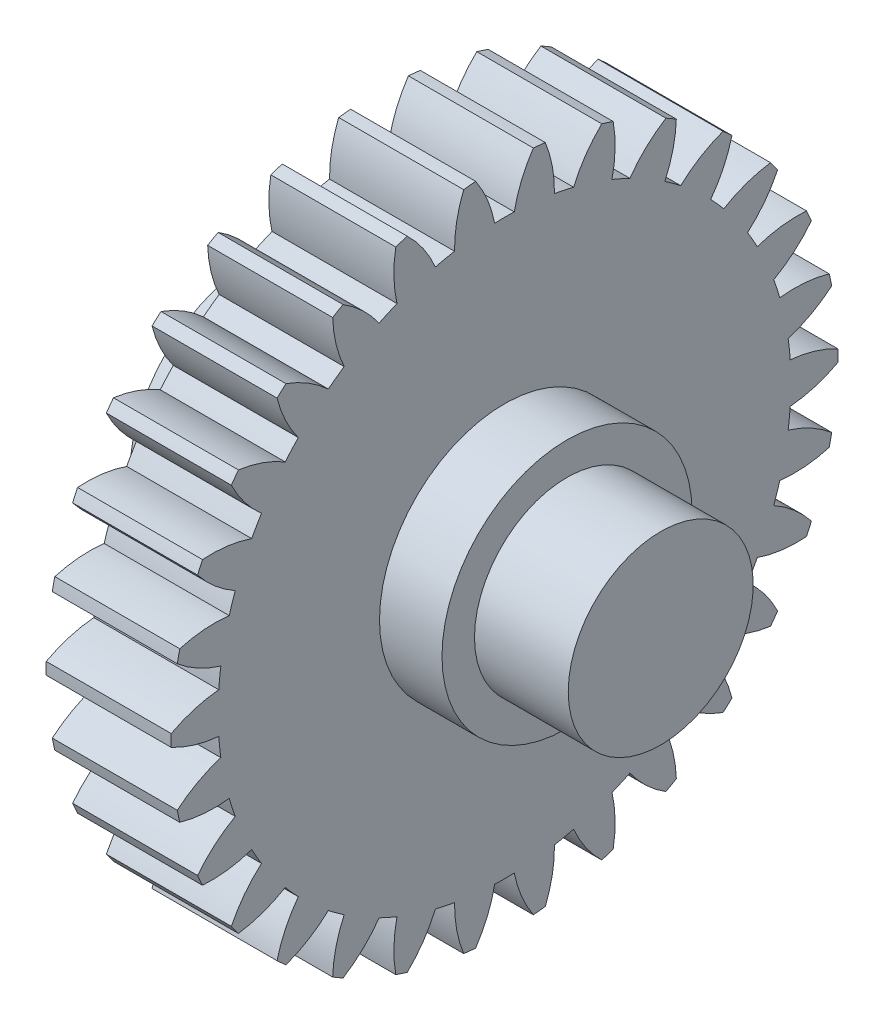
SolidWorks part; units mm, degrees
ref_plane "Plane1" through (0, 0, 0) normal (0, 0, 1) x (1, 0, 0)
ref_plane "Plane2" through (0, 0, 0) normal (0, 1, 0) x (1, 0, 0)
ref_plane "Plane3" through (0, 0, 0) normal (1, 0, 0) x (0, 0, -1)
other "Configuration Table"
sketch "HoldingSke" plane through (0, 0, 0) normal (0, 1, 0) x (1, 0, 0)
  line L0 (0, 0) -> (263.9645, -152.4)
  line L1 (-15, 0) -> (100, 0) construction
  line L2 (0, 0) -> (-2.1039, 2.3779)
  line L3 (0, 0) -> (-11.863, 4.5341)
  line L4 (0, 0) -> (7.479, 4.318)
  line L5 (0, 0) -> (-47.5972, -17.7524)
  line L6 (0, 0) -> (-10.5278, -7.1032)
  line L7 (-2.1039, 2.3779) -> (8.8311, 51.9886)
  line L8 (-76.2, 54.61) -> (-54.9402, 54.61)
  line L9 (-71.009, 38.7566) -> (-53.1078, 45.2721)
  line L10 (-76.2, 71.12) -> (104.1128, 71.12)
  line L11 (0, 0) -> (-12.7, 0)
  line L12 (-76.2, 101.6) -> (-76.1147, 101.6)
  line L13 (24.9733, 27.94) -> (52.9518, 28.4284)
  line L14 (24.9733, 27.94) -> (24.9746, 27.94)
  line L15 (24.9733, 27.94) -> (100.4006, 29.5858)
  circle A0 centre (0, 0) radius 9.525
  circle A1 centre (0, 0) radius 29.1029
  circle A2 centre (0, 0) radius 38.1
  circle A3 centre (0, 0) radius 9.525
  dimension "MHD" = 58.2058
  dimension "Hub_dia" = 76.2
  dimension "Bore" = 19.05
  dimension "MBD" = 19.05
  dimension "Num_teeth" = 30
  dimension "Pitch" = 304.8
  dimension "Overall_len" = 50.8
  dimension "Show_teeth" = 30
  dimension "Thickness" = 12.7
  dimension "OAL" = 50.8015
  dimension "T_dim" = 21.2598
  dimension "Ap" = 20
  dimension "H" = 19.05
  dimension "Pitch_radius" = 180.3128
  dimension "Width" = 12.7
  dimension "Backlash" = 0.0853
  dimension "Addendum_fac" = 1
  dimension "Dedendum_fac" = 1.25
  dimension "Clearance_fac" = 0.25
  dimension "Dedendum_add" = 0.0013
sketch "BasProSke" plane through (0, 0, 0) normal (0, 1, 0) x (1, 0, 0)
  line L0 (-10, 0) -> (60, 0) construction
  line L1 (0, 0) -> (0, 33.8667)
  line L2 (0, 0) -> (12.7, 0)
  line L3 (12.7, 0) -> (12.7, 33.8667)
  line L4 (12.7, 33.8667) -> (0, 33.8667)
  dimension "Thickness" = 12.7
  dimension "Diameter" = 67.7333
revolve "Base-Revolve" add sketch "BasProSke" angle 360 about L0
sketch "TooCutSke" plane through (0, 0, 0) normal (1, 0, 0) x (0, 0, -1)
  line L1 (0, 0) -> (0, 107) construction
  line L2 (0, 0) -> (-1.811, 31.6983) construction
  line L3 (0, 0) -> (-6.63, 63.0805) construction
  line L4 (-1.811, 31.6983) -> (-3.315, 31.5402) construction
  arc A0 (0.9953, 29.0859) -> (-0.9953, 29.0859) centre (0, 0) ccw
  arc A1 (2.9488, 33.7635) -> (-2.9488, 33.7635) centre (0, 0) ccw
  circle A2 centre (0, 0) radius 31.75 construction
  circle A3 centre (0, 0) radius 29.8352 construction
  arc A4 (-0.9953, 29.0859) -> (-2.9488, 33.7635) centre (-13.4553, 26.6289) ccw
  arc A5 (2.9488, 33.7635) -> (0.9953, 29.0859) centre (13.4553, 26.6289) ccw
  dimension "Root_dia" = 58.2058
  dimension "Overcut_dia" = 67.7841
  dimension "Pitch_dia" = 63.5
  dimension "Base_dia" = 59.6705
  dimension "Flank_rad" = 12.7
  dimension "Half_ang" = 6
  dimension "Half_CT" = 1.5123
extrude "ToothCut" cut sketch "TooCutSke" along normal through all
fillet "Breaks" [suppressed] radius 0.0423 tangent propagation no
fillet "RootFillets" [suppressed] radius 0.5304
pattern_circular "TeethCuts" count 30 every 12 about axis through (-10, 0, 0) along (1, 0, 0) of "ToothCut", "RootFillets", "Breaks"
sketch "HubNeaOneSke" plane through (0, 0, 0) normal (-1, 0, 0) x (0, 0, 1)
  circle A0 centre (0, 0) radius 29.1029
  dimension "Diameter" = 58.2058
extrude "HubNearOne" [suppressed] add sketch "HubNeaOneSke" along normal blind 38.1015
sketch "HubNeaBotSke" plane through (0, 0, 0) normal (-1, 0, 0) x (0, 0, 1)
  circle A0 centre (0, 0) radius 29.1029
  dimension "Diameter" = 58.2058
extrude "HubNearBoth" [suppressed] add sketch "HubNeaBotSke" along normal blind 19.0508
ref_plane "FarPln" through (12.7, 0, 0) normal (1, 0, 0) x (0, 0, -1)
sketch "HubFarSke" plane through (12.7, 0, 0) normal (1, 0, 0) x (0, 0, -1)
  circle A0 centre (0, 0) radius 29.1029
  dimension "Diameter" = 58.2058
extrude "HubFar" [suppressed] add sketch "HubFarSke" along normal blind 19.0508
sketch "Sketch1" plane through (0, 0, 0) normal (-1, 0, 0) x (0, 0, 1)
  circle A0 centre (0, 0) radius 12.7
  circle A1 centre (0, 0) radius 5.08
  dimension "D1" = 10.16
  dimension "D2" = 25.4
extrude "Boss-Extrude2" add sketch "Sketch1" along normal blind 12.7
sketch "Sketch3" plane through (0, 0, 0) normal (0, 1, 0) x (1, 0, 0)
  line L0 (0, 0.9953) -> (0, -0.9953) construction
  line L2 (-12.7, 0) -> (0, 0) construction
  circle A0 centre (-6.35, 0) radius 3.302
  dimension "D1" = 6.604
  dimension "D2" = 6.35
extrude "Cut-Extrude1" cut sketch "Sketch3" along normal through all
sketch "Sketch4" plane through (0, 0, 0) normal (0, 1, 0) x (1, 0, 0)
  line L1 (-3.527, 4.8895) -> (-9.173, 4.8895)
  line L2 (-9.173, 4.8895) -> (-11.9959, 0)
  line L3 (-11.9959, 0) -> (-9.173, -4.8895)
  line L4 (-9.173, -4.8895) -> (-3.527, -4.8895)
  line L5 (-3.527, -4.8895) -> (-0.7041, 0)
  line L6 (-0.7041, 0) -> (-3.527, 4.8895)
  line L7 (0, 12.7) -> (-12.7, 12.7) construction
  circle A0 centre (-6.35, 0) radius 4.8895 construction
  dimension "D1" = 9.779
extrude "Cut-Extrude2" cut sketch "Sketch4" along normal blind 8.255 contours L3 L4 L5 L6 L1 L2
sketch "Sketch5" plane through (12.7, 0, 0) normal (1, 0, 0) x (0, 0, -1)
  circle A0 centre (0, 0) radius 12.7
  dimension "D1" = 25.4
extrude "Boss-Extrude3" add sketch "Sketch5" along normal blind 6.35
sketch "Sketch6" plane through (19.05, 0, 0) normal (1, 0, 0) x (0, 0, -1)
  circle A0 centre (0, 0) radius 9.398
  dimension "D1" = 18.796
extrude "Boss-Extrude4" add sketch "Sketch6" along normal blind 9.525
equation "' \"Pitch@HoldingSke\" = 4"
equation "' \"Num_teeth@HoldingSke\" = 12"
equation "' \"Ap@HoldingSke\" =  20"
equation "' \"Ap@HoldingSke\" = 20"
equation "' \"Width@HoldingSke\" = 0.5"
equation "' \"Hub_dia@HoldingSke\"= 1"
equation "' \"Hub_dia@HoldingSke\" = 1"
equation "' \"Overall_len@HoldingSke\" = 1.0"
equation "' \"Bore@HoldingSke\" = 0.75"
equation "' \"T_dim@HoldingSke\" = 0.85"
equation "' \"Width@KeySke\" = 0.25"
equation "' \"Show_teeth@HoldingSke\" = 13"
equation "' \"Backlash@HoldingSke\" = 0.009"
equation "' \"Addendum_fac@HoldingSke\" = 1.0"
equation "' \"Dedendum_fac@HoldingSke\" = 1.25"
equation "' \"Dedendum_add@HoldingSke\" = 0.00005"
equation "' \"Clearance_fac@HoldingSke\" = 0.25"
equation "' \"Pitch@HoldingSke\" = 0.5"
equation "' \"Num_teeth@HoldingSke\" = 23"
equation "' \"Show_teeth@HoldingSke\" = 23"
equation "' \"Backlash@HoldingSke\" = 0.0375"
equation "\"Overcut_dia@TooCutSke\" = (\"Num_teeth@HoldingSke\" + 2 * \"Addendum_fac@HoldingSke\") / \"Pitch@HoldingSke\" + 0.002"
equation "\"Pitch_dia@TooCutSke\" = \"Num_teeth@HoldingSke\" / \"Pitch@HoldingSke\""
equation "\"Base_dia@TooCutSke\" = \"Num_teeth@HoldingSke\" / \"Pitch@HoldingSke\" * cos((\"Ap@HoldingSke\"  * 3.14159265 / 180))"
equation "\"Root_dia@TooCutSke\" = (\"Num_teeth@HoldingSke\" + 2) / \"Pitch@HoldingSke\" - 2 * (\"Addendum_fac@HoldingSke\" + \"Dedendum_fac@HoldingSke\") / \"Pitch@HoldingSke\" - \"Dedendum_add@HoldingSke\" * 2"
equation "\"Half_ang@TooCutSke\" = 180 / \"Num_teeth@HoldingSke\""
equation "\"Half_CT@TooCutSke\" = \"Num_teeth@HoldingSke\" / \"Pitch@HoldingSke\" * sin((3.14159265 / 2 / \"Num_teeth@HoldingSke\")) / 2 - 7 * \"Backlash@HoldingSke\" / 4"
equation "\"Flank_rad@TooCutSke\" = \"Num_teeth@HoldingSke\" / \"Pitch@HoldingSke\" / 5"
equation "\"Radius@RootFillets\" = \"Clearance_fac@HoldingSke\" / \"Pitch@HoldingSke\" + \"Dedendum_add@HoldingSke\""
equation "\"Break_rad@Breaks\" = 0.02 / \"Pitch@HoldingSke\""
equation "\"Thickness@HoldingSke\" = \"Width@HoldingSke\""
equation "\"OAL@HoldingSke\" = \"Thickness@HoldingSke\""
equation "\"MHD@HoldingSke\" = (\"Num_teeth@HoldingSke\" + 2) / \"Pitch@HoldingSke\" - 2 * (\"Addendum_fac@HoldingSke\" + \"Dedendum_fac@HoldingSke\")  / \"Pitch@HoldingSke\" - \"Dedendum_add@HoldingSke\" * 2"
equation "\"MBD@HoldingSke\" = (\"Num_teeth@HoldingSke\" + 2) / \"Pitch@HoldingSke\" - 2 * (\"Addendum_fac@HoldingSke\" + \"Dedendum_fac@HoldingSke\")  / \"Pitch@HoldingSke\" - \"Dedendum_add@HoldingSke\" * 2 - 0.002"
equation "\"MHD@HoldingSke\" = ((sgn( \"MHD@HoldingSke\" - \"Hub_dia@HoldingSke\" )-1)*( \"MHD@HoldingSke\" - \"Hub_dia@HoldingSke\" ))/-2+ \"Hub_dia@HoldingSke\""
equation "\"MBD@HoldingSke\" = ((sgn( \"MBD@HoldingSke\" - \"Bore@HoldingSke\" )-1)*( \"MBD@HoldingSke\" - \"Bore@HoldingSke\" ))/-2+ \"Bore@HoldingSke\""
equation "\"OAL@HoldingSke\" = ((sgn( \"OAL@HoldingSke\" - \"Overall_len@HoldingSke\" )+1)*( \"OAL@HoldingSke\" - \"Overall_len@HoldingSke\" ))/2 + \"Overall_len@HoldingSke\" + 0.000002"
equation "\"Num_teeth@TeethCuts\" = int( \"Show_teeth@HoldingSke\" ) + 1"
equation "\"Num_teeth@TeethCuts\" = ((sgn( \"Num_teeth@TeethCuts\" - \"Num_teeth@HoldingSke\" )-1)*( \"Num_teeth@TeethCuts\" - \"Num_teeth@HoldingSke\" ))/-2+ \"Num_teeth@HoldingSke\""
equation "\"Num_teeth@TeethCuts\" = ((sgn( \"Num_teeth@TeethCuts\" - 2.0)+1)*( \"Num_teeth@TeethCuts\" - 2.0))/2 +2.0"
equation "\"Angle@TeethCuts\" = 360.0 / \"Num_teeth@HoldingSke\""
equation "\"Diameter@BasProSke\" = (\"Num_teeth@HoldingSke\" + 2 * \"Addendum_fac@HoldingSke\") / \"Pitch@HoldingSke\""
equation "\"Thickness@BasProSke\"  = \"Thickness@HoldingSke\""
equation "' \"Fillet_rad@BasProSke\" =  \"Thickness@HoldingSke\" * 0.05"
equation "' \"Fillet_rad@BasProSke\" = \"Thickness@HoldingSke\" * 0.05"
equation "\"MHD@HoldingSke\" = ((sgn( \"MHD@HoldingSke\" - \"Root_dia@TooCutSke\" )-1)*( \"MHD@HoldingSke\" - \"Root_dia@TooCutSke\" ))/-2+ \"Root_dia@TooCutSke\""
equation "\"Diameter@HubNeaOneSke\" = \"MHD@HoldingSke\""
equation "\"Length@HubNearOne\" = \"OAL@HoldingSke\" - \"Thickness@BasProSke\""
equation "\"Diameter@HubNeaBotSke\" = \"MHD@HoldingSke\""
equation "\"Length@HubNearBoth\" = ( \"OAL@HoldingSke\" - \"Thickness@BasProSke\" ) / 2.0"
equation "\"Thickness@FarPln\" = \"Thickness@BasProSke\""
equation "\"Diameter@HubFarSke\" = \"MHD@HoldingSke\""
equation "\"Length@HubFar\" = ( \"OAL@HoldingSke\" - \"Thickness@BasProSke\" ) / 2.0"
equation "\"Diameter@BorSke\" = \"MBD@HoldingSke\""
equation "\"D1\"= \"OAL@HoldingSke\" * 2.0"
equation "\"Offset@KeySke\" = \"T_dim@HoldingSke\" - \"MBD@HoldingSke\" / 2.0"
